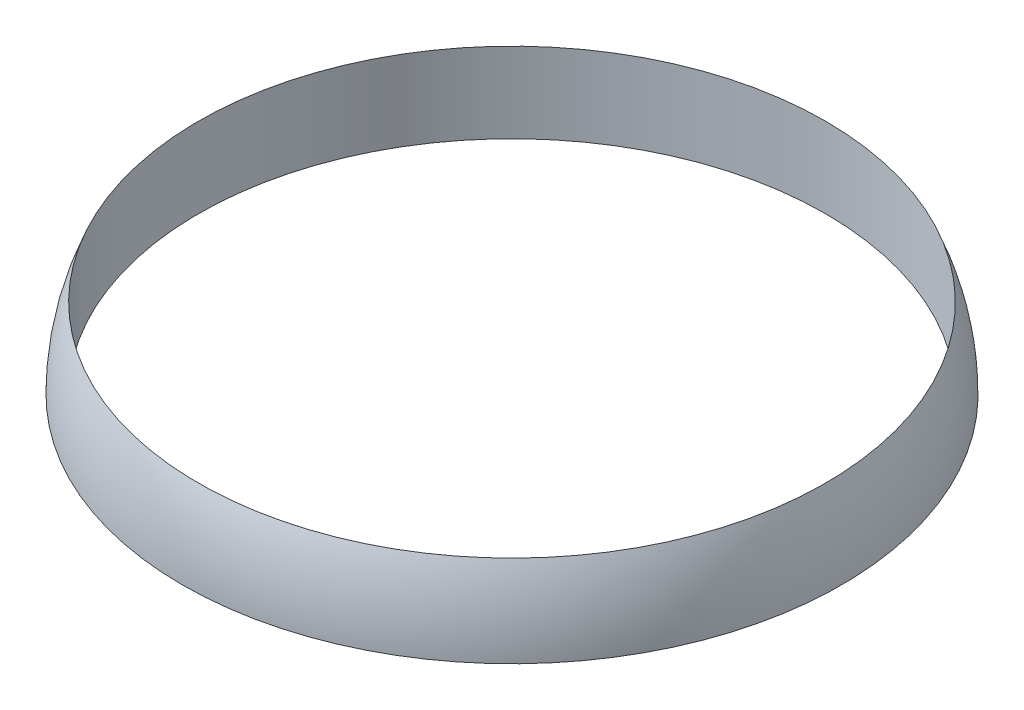
SolidWorks part; units mm, degrees
material "CFRP Filament"
ref_plane "Front Plane" through (0, 0, 0) normal (0, 0, 1) x (1, 0, 0)
ref_plane "Top Plane" through (0, 0, 0) normal (0, 1, 0) x (1, 0, 0)
ref_plane "Right Plane" through (0, 0, 0) normal (1, 0, 0) x (0, 0, -1)
sketch "Sketch1" plane through (0, 0, 0) normal (1, 0, 0) x (0, 0, -1)
  line L0 (78.2, 0) -> (78.2, 20)
  line L1 (78.2, 0) -> (82.2, 0)
  line L2 (0, 0) -> (0, 45.7169) construction
  arc A1 (82.2, 0) -> (78.2, 20) centre (30.2, 0) ccw
  dimension "D1" = 4
  dimension "D2" = 20
  dimension "D3" = 78.2
revolve "Revolve1" add sketch "Sketch1" angle 360 about L2
